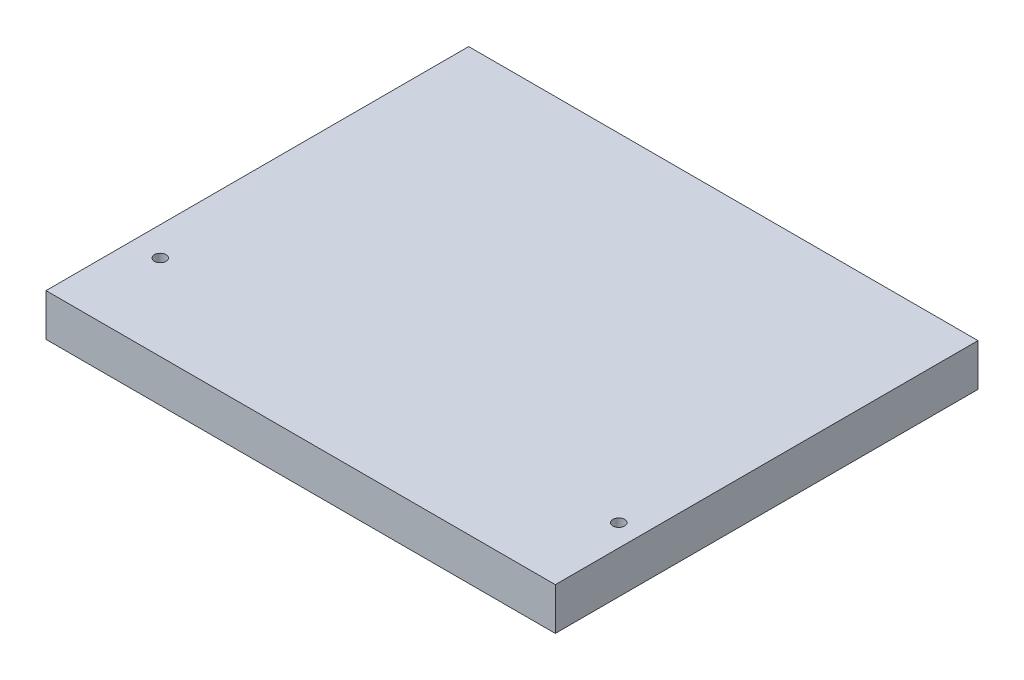
SolidWorks part; units mm, degrees
material "Polyurethane Foam Rigid"
ref_plane "X-Y Datum" through (0, 0, 0) normal (0, 0, 1) x (1, 0, 0)
ref_plane "X-Z Datum" through (0, 0, 0) normal (0, 1, 0) x (1, 0, 0)
ref_plane "Y-Z Datum" through (0, 0, 0) normal (1, 0, 0) x (0, 0, -1)
sketch "Sketch1" plane through (0, 0, 0) normal (0, 0, 1) x (1, 0, 0)
  line L1 (-153.0248, -12.7) -> (153.0248, -12.7)
  line L2 (-153.0248, -12.7) -> (-153.0248, 12.7)
  line L3 (-153.0248, 12.7) -> (153.0248, 12.7)
  line L4 (153.0248, -12.7) -> (153.0248, 12.7)
  line L5 (-153.0248, -12.7) -> (153.0248, 12.7) construction
  line L6 (-153.0248, 12.7) -> (153.0248, -12.7) construction
  point P0 (0, 0)
  dimension "D1" = 25.4
  dimension "D2" = 306.0497
extrude "Boss-Extrude1" add sketch "Sketch1" against normal blind 254
sketch "Sketch3" plane through (0, 12.7, 0) normal (0, 1, 0) x (1, 0, 0)
  line L0 (-153.0248, 254) -> (-153.0248, 0) construction
  line L1 (153.0248, 0) -> (-153.0248, 0) construction
  line L2 (153.0248, 254) -> (153.0248, 0) construction
  circle A0 centre (-135.6657, 51.2834) radius 3.5
  circle A1 centre (139.8613, 51.2834) radius 3.5
  dimension "D1" = 7
  dimension "D2" = 7
  dimension "D3" = 17.3591
  dimension "D4" = 51.2834
  dimension "D5" = 51.2834
  dimension "D6" = 13.1635
extrude "Cut-Extrude1" cut sketch "Sketch3" against normal through all
